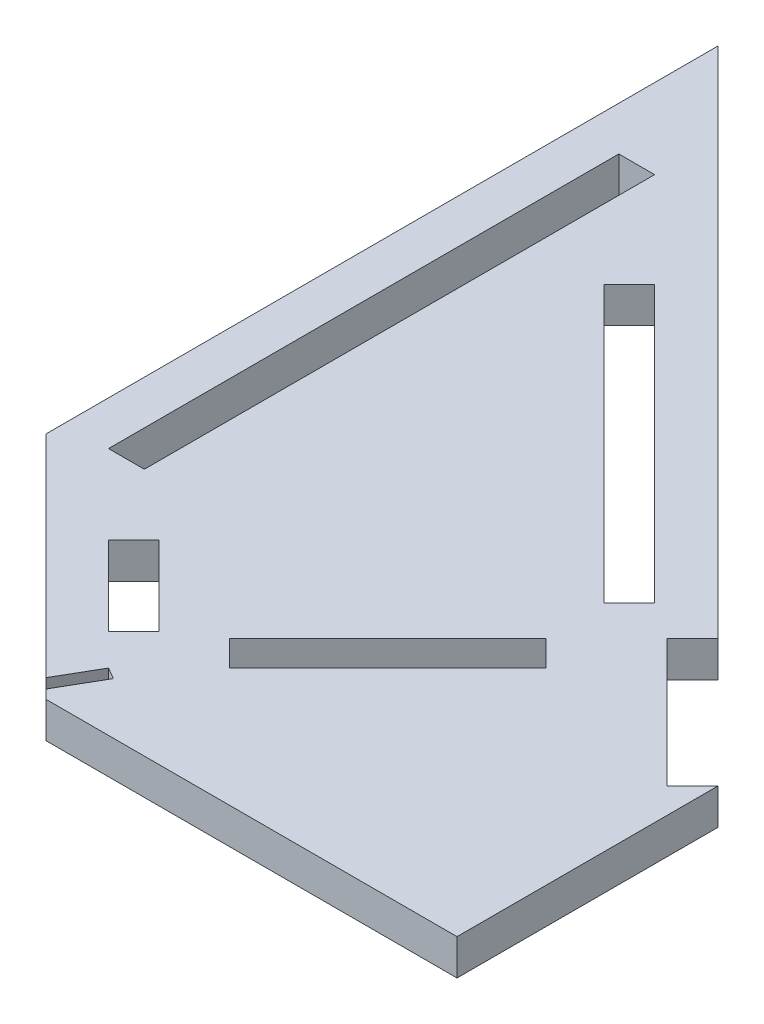
SolidWorks part; units mm, degrees
ref_plane "Front Plane" through (0, 0, 0) normal (0, 0, 1) x (1, 0, 0)
ref_plane "Top Plane" through (0, 0, 0) normal (0, 1, 0) x (1, 0, 0)
ref_plane "Right Plane" through (0, 0, 0) normal (1, 0, 0) x (0, 0, -1)
sketch "Sketch1" plane through (0, 0, 0) normal (0, 1, 0) x (1, 0, 0)
  line L0 (0, 0) -> (0, 58.25)
  line L1 (0, 58.25) -> (-143.0789, 201.3289)
  line L2 (-143.0789, 201.3289) -> (-143.0789, 51.3289)
  line L3 (-143.0789, 51.3289) -> (-95.9462, 4.1962)
  line L4 (-91.75, 0) -> (0, 0)
  line L5 (-93.75, 2) -> (-91.75, 0)
  line L6 (-82.9929, 32.1972) -> (-77.336, 26.5404) construction
  line L7 (-47.6375, 67.5525) -> (-82.9929, 32.1972) construction
  line L8 (-47.6375, 67.5525) -> (-41.9807, 61.8957) construction
  line L9 (-298.2472, -352.1996) -> (-88.2472, 11.5311)
  line L10 (-88.2472, 11.5311) -> (-90.8453, 13.0311)
  line L11 (-90.8453, 13.0311) -> (-300.8453, -350.6996)
  line L12 (-300.8453, -350.6996) -> (-298.2472, -352.1996)
  line L13 (-93.75, 2) -> (-88.2472, 11.5311)
  line L14 (-88.2472, 11.5311) -> (-90.8453, 13.0311)
  line L15 (-90.8453, 13.0311) -> (-95.9462, 4.1962)
  line L17 (-41.9807, 61.8957) -> (-77.336, 26.5404) construction
  line L18 (-109.7154, 142.5174) -> (-48.0839, 80.886)
  line L19 (-48.0839, 80.886) -> (-42.4271, 86.5429)
  line L20 (-42.4271, 86.5429) -> (-104.0585, 148.1743)
  line L21 (-104.0585, 148.1743) -> (-109.7154, 142.5174)
  line L22 (-109.7154, 142.5174) -> (-48.0839, 80.886)
  line L23 (-48.0839, 80.886) -> (-42.4271, 86.5429)
  line L24 (-42.4271, 86.5429) -> (-104.0585, 148.1743)
  line L25 (-104.0585, 148.1743) -> (-109.7154, 142.5174)
  line L34 (-125.2717, 55.4575) -> (-125.2717, 169.3875)
  line L35 (-125.2717, 169.3875) -> (-133.2717, 169.3875)
  line L36 (-133.2717, 169.3875) -> (-133.2717, 55.4575)
  line L37 (-133.2717, 55.4575) -> (-125.2717, 55.4575)
  line L38 (-125.2717, 55.4575) -> (-125.2717, 169.3875)
  line L39 (-125.2717, 169.3875) -> (-133.2717, 169.3875)
  line L40 (-133.2717, 169.3875) -> (-133.2717, 55.4575)
  line L41 (-133.2717, 55.4575) -> (-125.2717, 55.4575)
  line L42 (-82.9929, 32.1972) -> (-77.336, 26.5404)
  line L43 (-47.6375, 67.5525) -> (-82.9929, 32.1972)
  line L44 (-47.6375, 67.5525) -> (-41.9807, 61.8957)
  line L45 (-41.9807, 61.8957) -> (-77.336, 26.5404)
  line L47 (-115.594, 37.7798) -> (-97.9164, 20.1022)
  line L50 (-97.9164, 20.1022) -> (-92.2595, 25.759)
  line L52 (-92.2595, 25.759) -> (-109.9372, 43.4367)
  line L54 (-109.9372, 43.4367) -> (-115.594, 37.7798)
  line L55 (-34.1283, 81.0618) -> (-5.6602, 52.5937)
  line L56 (-5.6602, 52.5937) -> (-0.0033, 58.2506)
  line L57 (-0.0033, 58.2506) -> (-28.4714, 86.7187)
  line L58 (-28.4714, 86.7187) -> (-34.1283, 81.0618)
  line L59 (-34.1283, 81.0618) -> (-5.6602, 52.5937)
  line L60 (-5.6602, 52.5937) -> (-0.0033, 58.2506)
  line L61 (-0.0033, 58.2506) -> (-28.4714, 86.7187)
  line L62 (-28.4714, 86.7187) -> (-34.1283, 81.0618)
  line L63 (-115.594, 37.7798) -> (-97.9164, 20.1022)
  line L64 (-97.9164, 20.1022) -> (-92.2595, 25.759)
  line L65 (-92.2595, 25.759) -> (-109.9372, 43.4367)
  line L66 (-109.9372, 43.4367) -> (-115.594, 37.7798)
  dimension "D1" = 135
  dimension "D2" = 150
  dimension "D3" = 72.59
  dimension "D4" = 91.75
  dimension "D5" = 0
  dimension "D6" = 0
  dimension "D7" = 0
  dimension "D8" = 0
  dimension "D9" = 0
extrude "Boss-Extrude1" add sketch "Sketch1" along normal blind 8 contours L62 L1 L2 L3 L15 L14 L13 L5 L4 L0 L59 L41 L40 L39 L38 L25 L24 L23 L22 L44 L45 L42 L43 region at (-80.4323, 0, -73.1393)
